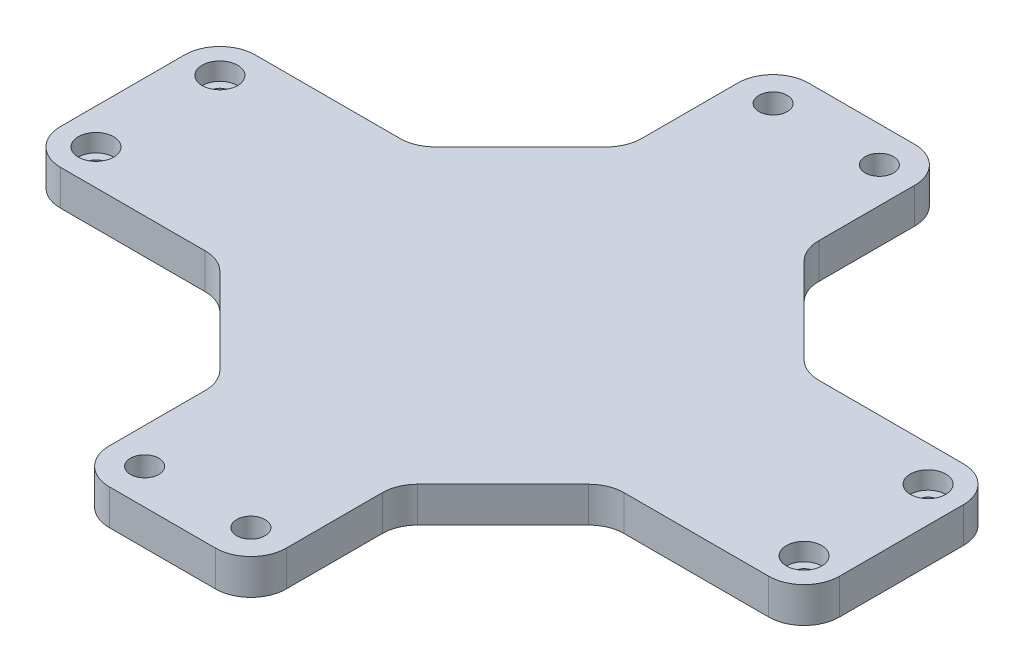
SolidWorks part; units mm, degrees
ref_plane "前视基准面" through (0, 0, 0) normal (0, 0, 1) x (1, 0, 0)
ref_plane "上视基准面" through (0, 0, 0) normal (0, 1, 0) x (1, 0, 0)
ref_plane "右视基准面" through (0, 0, 0) normal (1, 0, 0) x (0, 0, -1)
sketch "草图1" plane through (0, 0, 0) normal (0, 1, 0) x (1, 0, 0)
  line L0 (-47, 10) -> (-47, -10) construction
  line L1 (54.75, -31.5) -> (-54.75, -31.5) construction
  line L2 (54.75, -31.5) -> (54.75, 31.5) construction
  line L3 (54.75, 31.5) -> (-54.75, 31.5) construction
  line L4 (-54.75, -31.5) -> (-54.75, 31.5) construction
  line L5 (54.75, -31.5) -> (-54.75, 31.5) construction
  line L6 (54.75, 31.5) -> (-54.75, -31.5) construction
  line L7 (-29.75, 7) -> (-29.75, -7) construction
  line L8 (50.25, 7) -> (50.25, -7) construction
  line L9 (50.25, 0) -> (-29.75, 0) construction
  line L10 (-29.75, 0) -> (-47, 0) construction
  line L11 (-29.75, 7) -> (50.25, 7) construction
  circle A0 centre (-47, 10) radius 1.05
  circle A1 centre (-47, -10) radius 1.05
  circle A2 centre (-29.75, 7) radius 1.05
  circle A3 centre (-29.75, -7) radius 1.05
  circle A4 centre (50.25, 7) radius 1.05
  circle A5 centre (50.25, -7) radius 1.05
  point P0 (0, 0)
  point P20 (0, 0)
  dimension "D8" = 2.1
  dimension "D1" = 63
  dimension "D2" = 109.5
  dimension "D3" = 14
  dimension "D4" = 20
  dimension "D5" = 4.5
  dimension "D6" = 80
  dimension "D7" = 17.25
sketch "草图2" plane through (0, 0, 0) normal (0, 1, 0) x (1, 0, 0)
  line L0 (50.25, 0) -> (-29.75, 0) construction
  line L1 (54.25, -11) -> (-33.75, -11)
  line L2 (54.25, -11) -> (54.25, 11)
  line L3 (54.25, 11) -> (-33.75, 11)
  line L4 (-33.75, -11) -> (-33.75, 11)
  line L5 (54.25, -11) -> (-33.75, 11) construction
  line L6 (54.25, 11) -> (-33.75, -11) construction
  line L7 (50.25, 7) -> (50.25, -7) construction
  line L8 (-29.75, 7) -> (50.25, 7) construction
  line L9 (10.25, 25.25) -> (10.25, -25.25) construction
  line L10 (20.25, -39.5) -> (0.25, -39.5)
  line L11 (20.25, -39.5) -> (20.25, -11)
  line L12 (20.25, -11) -> (0.25, -11)
  line L13 (0.25, -39.5) -> (0.25, -11)
  line L14 (20.25, -39.5) -> (0.25, -11) construction
  line L15 (20.25, -11) -> (0.25, -39.5) construction
  line L16 (20.25, 39.5) -> (0.25, 39.5)
  line L17 (20.25, 39.5) -> (20.25, 11)
  line L18 (20.25, 11) -> (0.25, 11)
  line L19 (0.25, 39.5) -> (0.25, 11)
  line L20 (20.25, 39.5) -> (0.25, 11) construction
  line L21 (20.25, 11) -> (0.25, 39.5) construction
  line L22 (0.25, 11) -> (0.25, -11) construction
  line L23 (54.75, 31.5) -> (-54.75, 31.5) construction
  line L24 (4.25, 35.5) -> (16.25, 35.5) construction
  line L25 (16.25, 35.5) -> (16.25, -35.5) construction
  line L26 (16.25, -35.5) -> (4.25, -35.5) construction
  line L27 (4.25, -35.5) -> (4.25, 35.5) construction
  line L28 (10.25, 35.5) -> (10.25, 25.25) construction
  line L29 (16.25, 0) -> (10.25, 0) construction
  circle A0 centre (4.25, 35.5) radius 1.6
  circle A1 centre (-29.75, 7) radius 1.05
  circle A2 centre (-29.75, -7) radius 1.05
  circle A3 centre (50.25, 7) radius 1.05
  circle A4 centre (50.25, -7) radius 1.05
  circle A5 centre (16.25, 35.5) radius 1.6
  circle A6 centre (16.25, -35.5) radius 1.6
  circle A7 centre (4.25, -35.5) radius 1.6
  point P0 (10.25, 0)
  point P23 (10.25, -25.25)
  point P28 (10.25, 25.25)
  point P36 (10.25, 0)
  dimension "D1" = 2.1
  dimension "D6" = 3.2
  dimension "D2" = 4
  dimension "D3" = 4
  dimension "D4" = 8
  dimension "D5" = 20
  dimension "D7" = 4
  dimension "D8" = 4
extrude "凸台-拉伸1" add sketch "草图2" along normal blind 4 contours L4 L1 L2 L3 A4 A3 A2 A1 | L16 L19 L3 L17 | L13 L10 L11 L1 region at (10.25, 0, 0) region at (10.25, 0, 24.9524) region at (10.25, 0, -24.9524)
sketch "草图3" plane through (0, 4, 0) normal (0, 1, 0) x (1, 0, 0)
  circle A1 centre (-29.75, 7) radius 2
  circle A2 centre (-29.75, -7) radius 2
  circle A3 centre (50.25, 7) radius 2
  circle A4 centre (50.25, -7) radius 2
  dimension "D1" = 4
extrude "切除-拉伸1" cut sketch "草图3" against normal blind 2
chamfer "倒角1" distance 12 angle 45 4 edges at (0.25, 2, 11) (20.25, 2, 11) (20.25, 2, -11) (0.25, 2, -11)
fillet "圆角1" radius 4 16 edges at (-33.75, 2, -11) (20.25, 2, -39.5) (54.25, 2, -11) (54.25, 2, 11) (20.25, 2, 39.5) (0.25, 2, 39.5) (-33.75, 2, 11) (0.25, 2, -39.5) (0.25, 2, 23) (20.25, 2, 23) (32.25, 2, 11) (32.25, 2, -11) (20.25, 2, -23) (0.25, 2, -23) (-11.75, 2, -11) (-11.75, 2, 11)
